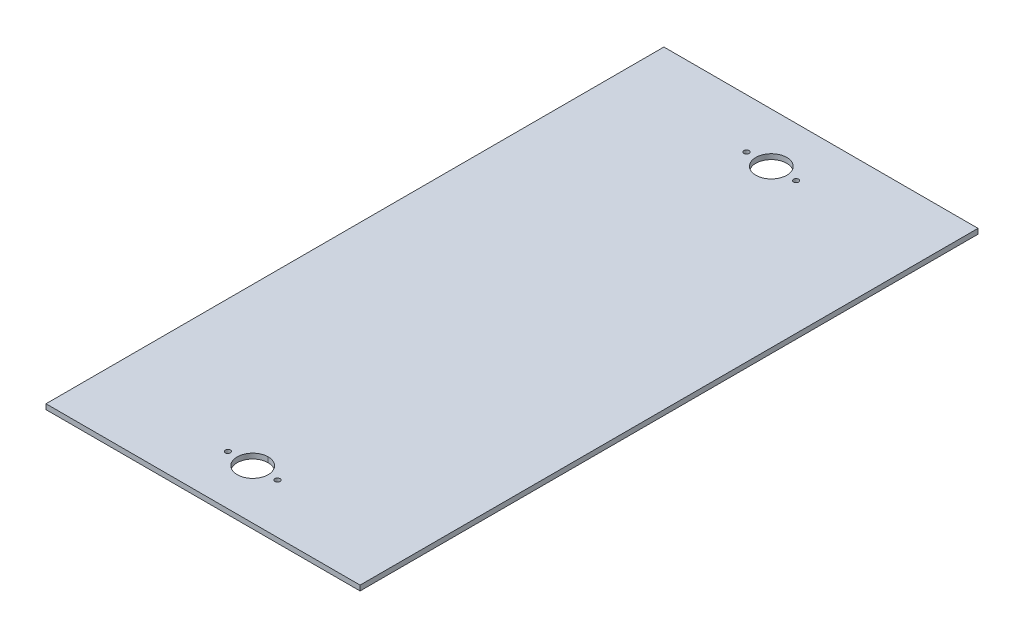
SolidWorks part; units mm, degrees
ref_plane "Front Plane" through (0, 0, 0) normal (0, 0, 1) x (1, 0, 0)
ref_plane "Top Plane" through (0, 0, 0) normal (0, 1, 0) x (1, 0, 0)
ref_plane "Right Plane" through (0, 0, 0) normal (1, 0, 0) x (0, 0, -1)
sketch "Sketch1" plane through (0, 0, 0) normal (0, 1, 0) x (1, 0, 0)
  line L1 (91.8972, 142.6972) -> (-91.8972, 142.6972)
  line L2 (91.8972, 142.6972) -> (91.8972, -142.6972)
  line L3 (91.8972, -142.6972) -> (-91.8972, -142.6972)
  line L4 (-91.8972, 142.6972) -> (-91.8972, -142.6972)
  line L5 (91.8972, 142.6972) -> (-91.8972, -142.6972) construction
  line L6 (91.8972, -142.6972) -> (-91.8972, 142.6972) construction
  point P0 (0, 0)
  dimension "D1" = 183.7944
  dimension "D2" = 285.3944
extrude "Boss-Extrude1" add sketch "Sketch1" along normal blind 2.9972
sketch "Sketch2" plane through (0, 2.9972, 0) normal (0, 1, 0) x (1, 0, 0)
  line L0 (0, -151.7472) -> (0, 151.7472) construction
  line L1 (-91.8972, -142.6972) -> (91.8972, -142.6972)
  line L2 (-91.8972, -142.6972) -> (-91.8972, -180.7972)
  line L3 (-91.8972, -180.7972) -> (91.8972, -180.7972)
  line L4 (91.8972, -142.6972) -> (91.8972, -180.7972)
  line L5 (-91.8972, 142.6972) -> (91.8972, 142.6972)
  line L6 (-91.8972, 142.6972) -> (-91.8972, 180.7972)
  line L7 (-91.8972, 180.7972) -> (91.8972, 180.7972)
  line L8 (91.8972, 142.6972) -> (91.8972, 180.7972)
  line L9 (91.8972, 180.7972) -> (129.9972, 180.7972)
  line L10 (91.8972, 180.7972) -> (91.8972, -180.7972)
  line L11 (91.8972, -180.7972) -> (129.9972, -180.7972)
  line L12 (129.9972, 180.7972) -> (129.9972, -180.7972)
  line L13 (-14.505, 151.7472) -> (14.505, 151.7472) construction
  line L14 (-14.505, -151.7472) -> (14.505, -151.7472) construction
  circle A0 centre (0, 151.7472) radius 7.55 construction
  circle A1 centre (0, -151.7472) radius 7.55 construction
  circle A2 centre (0, -151.7472) radius 9.055
  circle A3 centre (0, 151.7472) radius 9.055
  circle A4 centre (-14.505, 151.7472) radius 1.5
  circle A5 centre (14.505, 151.7472) radius 1.5
  circle A6 centre (-14.505, -151.7472) radius 1.5
  circle A7 centre (14.505, -151.7472) radius 1.5
  point P17 (0, 0)
  point P20 (0, 151.7472)
  point P32 (0, -151.7472)
  line M15 (-91.8972, -142.6972) -> (91.8972, -142.6972)
  line M17 (91.8972, 142.6972) -> (-91.8972, 142.6972)
  dimension "D1" = 15.1
  dimension "D2" = 1.5
  dimension "D6" = 14.505
  dimension "D7" = 3
  dimension "D3" = 38.1
  dimension "D4" = 38.1
  dimension "D5" = 1.505
extrude "Boss-Extrude2" add sketch "Sketch2" against normal up to surface (2.9972 mm away) contours L8 L7 L6 M17 | L4 L2 L3 M15 | L5 A3 | L1 A2 region at (0, 2.9972, 162.1509) region at (0, 2.9972, 142.6952) region at (0, 2.9972, -162.1509) region at (0, 2.9972, -142.6952) up to face at (0, 0, 0)
equation "\"wallthickness\"= .118in"
equation "\"floorThickness\"= .220in"
equation "\"D1@Sketch1\"=\"wallthickness\"*2+7in"
equation "\"D2@Sketch1\"=\"wallthickness\"*2+11in"
equation "\"D1@Boss-Extrude1\"=\"wallthickness\""
